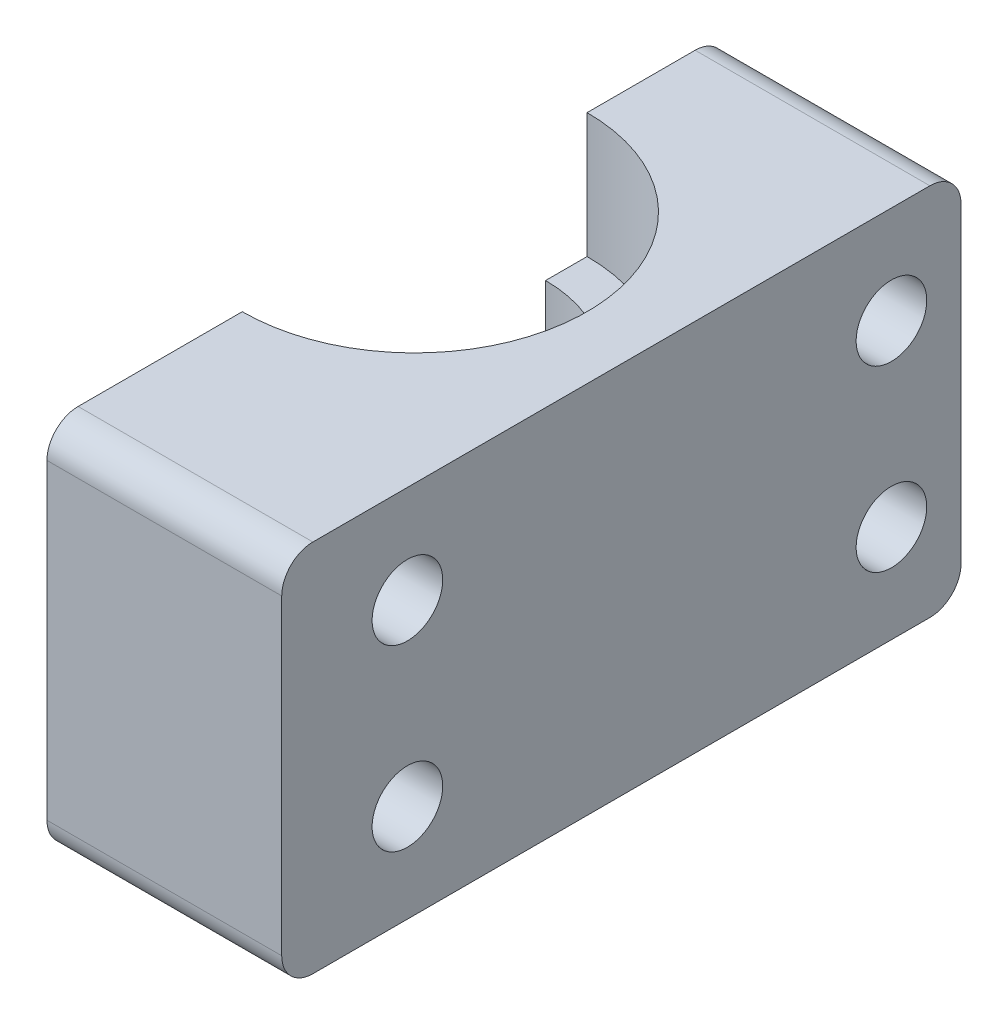
SolidWorks part; units mm, degrees
ref_plane "Front Plane" through (0, 0, 0) normal (0, 0, 1) x (1, 0, 0)
ref_plane "Top Plane" through (0, 0, 0) normal (0, 1, 0) x (1, 0, 0)
ref_plane "Right Plane" through (0, 0, 0) normal (1, 0, 0) x (0, 0, -1)
sketch "Sketch8" plane through (0, 0, 0) normal (1, 0, 0) x (0, 0, -1)
  line L1 (-15, 50) -> (15, 50)
  line L2 (-15, 50) -> (-15, -50)
  line L3 (-15, -50) -> (15, -50)
  line L4 (15, 50) -> (15, -50)
  line L5 (-15, 50) -> (15, -50) construction
  line L6 (-15, -50) -> (15, 50) construction
  point P0 (0, 0)
  dimension "D1" = 30
  dimension "D2" = 100
extrude "Boss-Extrude1" add sketch "Sketch8" along normal blind 100
sketch "Sketch7" plane through (0, 0, 0) normal (1, 0, 0) x (0, 0, -1)
  line L0 (-8.3, 9) -> (-150, 9)
  line L1 (15, 50) -> (-15, 50) construction
  line L2 (-8.3, 9) -> (-8.3, 3)
  line L3 (-8.3, 3) -> (-6.3, 3)
  line L4 (-6.3, 3) -> (-6.3, -3)
  line L5 (-6.3, -3) -> (-8.3, -3)
  line L6 (-8.3, -3) -> (-8.3, -9)
  line L11 (-8.3, -9) -> (-150, -9)
  line L12 (-150, -9) -> (-150, -50)
  line L13 (0, -50) -> (0, 50)
  line L14 (0, 55) -> (0, -55) construction
  line L15 (-150, 9) -> (-150, 50)
  line L16 (-150, 50) -> (0, 50)
  line L17 (-150, -50) -> (0, -50)
  line L18 (-15, -50) -> (15, -50) construction
  line L19 (-15, 9) -> (-15, -9) construction
  line L20 (-15, 50) -> (-15, -50) construction
  line L22 (16.5, 0) -> (-16.5, 0) construction
  point P29 (-15, 0)
  dimension "D1" = 8.3
  dimension "D2" = 6
  dimension "D3" = 6.3
  dimension "D4" = 6
  dimension "D5" = 18
  dimension "D9" = 150
revolve "Cut-Revolve3" cut sketch "Sketch7" angle 360 about L13
sketch "Sketch9" plane through (0, 9, 0) normal (0, 1, 0) x (1, 0, 0)
  line L0 (-55, 0) -> (55, 0) construction
  line L1 (11.3, -15) -> (100, -15)
  line L2 (11.3, -15) -> (11.3, 15)
  line L3 (11.3, 15) -> (100, 15)
  line L4 (100, -15) -> (100, 15)
  line L5 (11.3, -15) -> (100, 15) construction
  line L6 (11.3, 15) -> (100, -15) construction
  line L7 (100, 15) -> (100, -15) construction
  line L8 (0, -15) -> (100, -15) construction
  line L9 (8.3, 15) -> (8.3, -15) construction
  line L10 (100, 15) -> (0, 15) construction
  arc A1 (0, -8.3) -> (0, 8.3) centre (0, 0) ccw construction
  point P0 (55.65, 0)
  dimension "D1" = 3
extrude "Cut-Extrude1" cut sketch "Sketch9" against normal through all
sketch "Sketch10" plane through (0, 0, 0) normal (-1, 0, 0) x (0, 0, 1)
  line L0 (-11.65, 4.3) -> (-11.65, 9) construction
  line L1 (-11.65, -4.3) -> (11.65, -4.3) construction
  line L2 (-11.65, -4.3) -> (-11.65, 4.3) construction
  line L3 (-11.65, 4.3) -> (11.65, 4.3) construction
  line L4 (11.65, -4.3) -> (11.65, 4.3) construction
  line L5 (-11.65, -4.3) -> (11.65, 4.3) construction
  line L6 (-11.65, 4.3) -> (11.65, -4.3) construction
  line L7 (-15, 9) -> (-8.3, 9) construction
  circle A0 centre (-11.65, 4.3) radius 1.7
  circle A1 centre (-11.65, -4.3) radius 1.7
  circle A2 centre (11.65, -4.3) radius 1.7
  circle A3 centre (11.65, 4.3) radius 1.7
  point P0 (0, 0)
  dimension "D1" = 3.4
  dimension "D2" = 4.7
extrude "Cut-Extrude2" cut sketch "Sketch10" against normal through all
other "Move Face1" face at (5.65, 0, 15) offset 2.7 parameters "D1"=2.7
fillet "Fillet1" radius 1.5 4 edges at (5.65, 9, -15) (5.65, -9, -15) (5.65, -9, 17.7) (5.65, 9, 17.7)
equation "\"linear_bearing_l\"= 35"
equation "\"linear_bearing_d\"= 12"
equation "\"t\"= 3"
equation "\"axes_offset\"= 44.5"
equation "\"fan_b\"= 30"
equation "\"E3D_r\"= 12.8"
equation "\"fan_screws_b\"= 24"
equation "\"fan_screws_l\"= 15"
equation "\"M3_tap_d\"= 2.6"
equation "\"M3_d\"= 3.4"
equation "\"E3D_screws_l\"= 15"
equation "\"M3_nut_s\"= 5.9"
equation "\"M3_nut_m\"= 1.8"
equation "\"cable_ties_d\"= 3"
equation "\"D1@Sketch8\"=\"fan_b\""
equation "\"D2@Sketch8\"=100"
equation "\"D1@Sketch9\"=\"t\""
equation "\"D1@Sketch10\"=\"M3_d\""
equation "\"D2@Sketch10\"=\"M3_d\" / 2 + \"t\""
equation "\"D1@Fillet1\"=\"t\" / 2"
